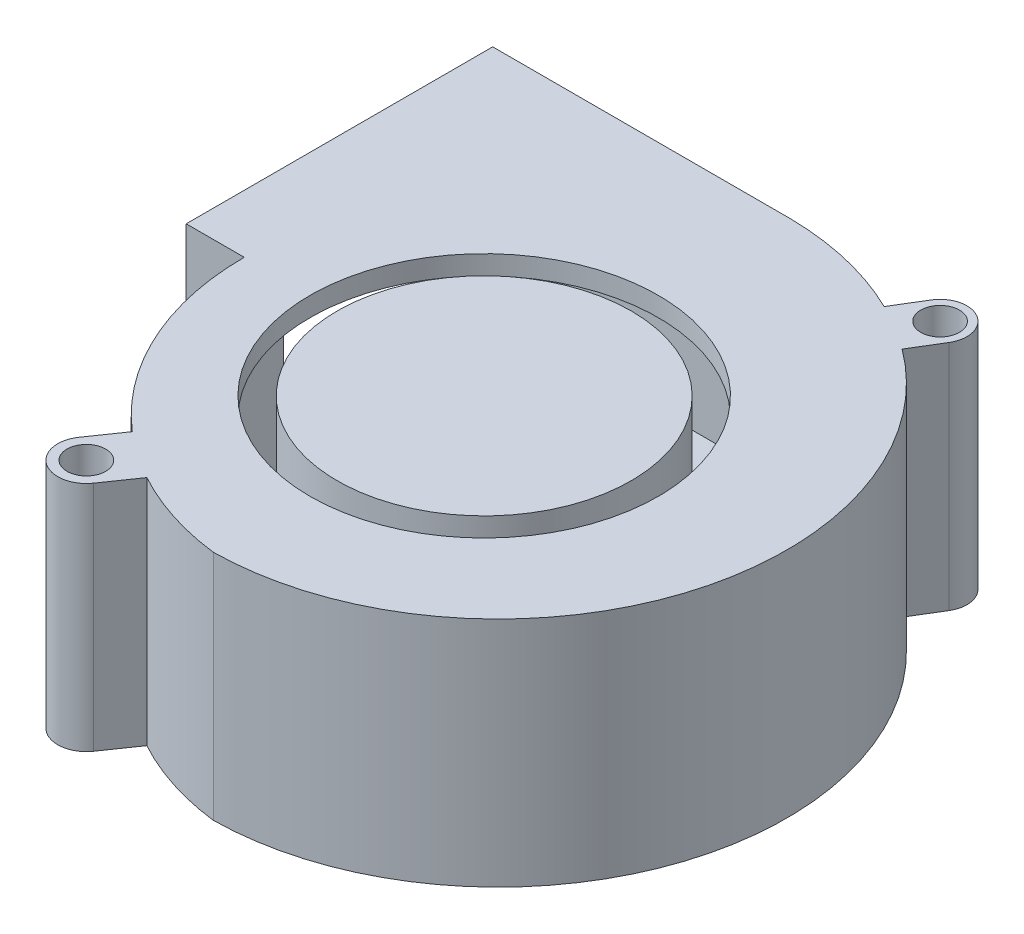
SolidWorks part; units mm, degrees
ref_plane "Front Plane" through (0, 0, 0) normal (0, 0, 1) x (1, 0, 0)
ref_plane "Top Plane" through (0, 0, 0) normal (0, 1, 0) x (1, 0, 0)
ref_plane "Right Plane" through (0, 0, 0) normal (1, 0, 0) x (0, 0, -1)
sketch "Sketch1" plane through (0, 0, 0) normal (0, 1, 0) x (1, 0, 0)
  line L0 (-37.65, 37.3) -> (-37.65, -2.3)
  line L1 (-37.65, -37.3) -> (37.65, -37.3) construction
  line L2 (-37.65, -37.3) -> (-37.65, 37.3) construction
  line L3 (-37.65, 37.3) -> (37.65, 37.3) construction
  line L4 (37.65, -37.3) -> (37.65, 37.3) construction
  line L5 (-37.65, -37.3) -> (37.65, 37.3) construction
  line L6 (-37.65, 37.3) -> (37.65, -37.3) construction
  line L7 (-37.65, -2.3) -> (-30.15, -2.3)
  line L8 (-37.65, 37.3) -> (0.85, 37.3)
  line L9 (-30.15, -2.3) -> (-30.15, -37.3) construction
  line L10 (-37.65, -2.3) -> (37.65, -2.3) construction
  line L11 (0.85, 37.3) -> (0.85, -37.2966) construction
  line L12 (-78.9719, 116.2867) -> (254.3615, 116.2867) construction
  line L13 (18.992, 37.3) -> (16.6976, 33.5295)
  line L14 (24.908, 33.7) -> (22.6135, 29.9295)
  line L15 (-20.6864, -33.1) -> (-17.8754, -29.0357)
  line L16 (-14.6136, -37.3) -> (-11.8027, -33.2357)
  arc A0 (0.85, 37.3) -> (16.6976, 33.5295) centre (0.3483, 0.0017) cw
  arc A1 (-30.15, -2.3) -> (-17.8754, -29.0357) centre (5.1043, -2.3) ccw
  circle A2 centre (0.85, -2.3) radius 22.5 construction
  arc A3 (18.992, 37.3) -> (24.908, 33.7) centre (21.95, 35.5) cw
  arc A4 (-14.6136, -37.3) -> (-20.6864, -33.1) centre (-17.65, -35.2) cw
  arc A5 (22.6135, 29.9295) -> (0.3483, -37.3) centre (0.3483, 0.0017) cw
  arc A6 (-11.8027, -33.2357) -> (0.85, -37.2966) centre (5.1043, -2.3) ccw
  point P0 (0, 0)
  point P19 (-12.7845, -37.3)
  dimension "D5" = 45
  dimension "D1" = 75.3
  dimension "D2" = 74.6
  dimension "D3" = 39.6
  dimension "D4" = 38.5
  dimension "D6" = 7.5
  dimension "D7" = 21.1
  dimension "D8" = 37.8
  dimension "D11" = 32.9
  dimension "D12" = 18.5
extrude "Boss-Extrude1" add sketch "Sketch1" along normal blind 30 contours L16 A6 A5 L14 A3 L13 A0 L8 L0 L7 A1 L15 A4 region at (-0.588, 0, -2.7238)
shell "Shell1" thickness 2.5 removed face at (-37.65, 15, -17.5)
sketch "Sketch2" plane through (0, 30, 0) normal (0, 1, 0) x (1, 0, 0)
  circle A0 centre (0.85, -2.3) radius 22.5 construction
  circle A1 centre (0.85, -2.3) radius 22.5
extrude "Cut-Extrude1" cut sketch "Sketch2" against normal blind 14
sketch "Sketch3" plane through (0, 2.5, 0) normal (0, 1, 0) x (1, 0, 0)
  circle A1 centre (0.85, -2.3) radius 19
  dimension "D1" = 38
extrude "Boss-Extrude2" add sketch "Sketch3" along normal up to surface (27.5 mm away) up to face at (0.85, 30, 24.8)
sketch "Sketch4" plane through (0, 30, 0) normal (0, 1, 0) x (1, 0, 0)
  circle A0 centre (21.95, 35.5) radius 2.5
  circle A1 centre (-17.65, -35.2) radius 2.5
  dimension "D1" = 5
extrude "Cut-Extrude2" cut sketch "Sketch4" against normal through all
